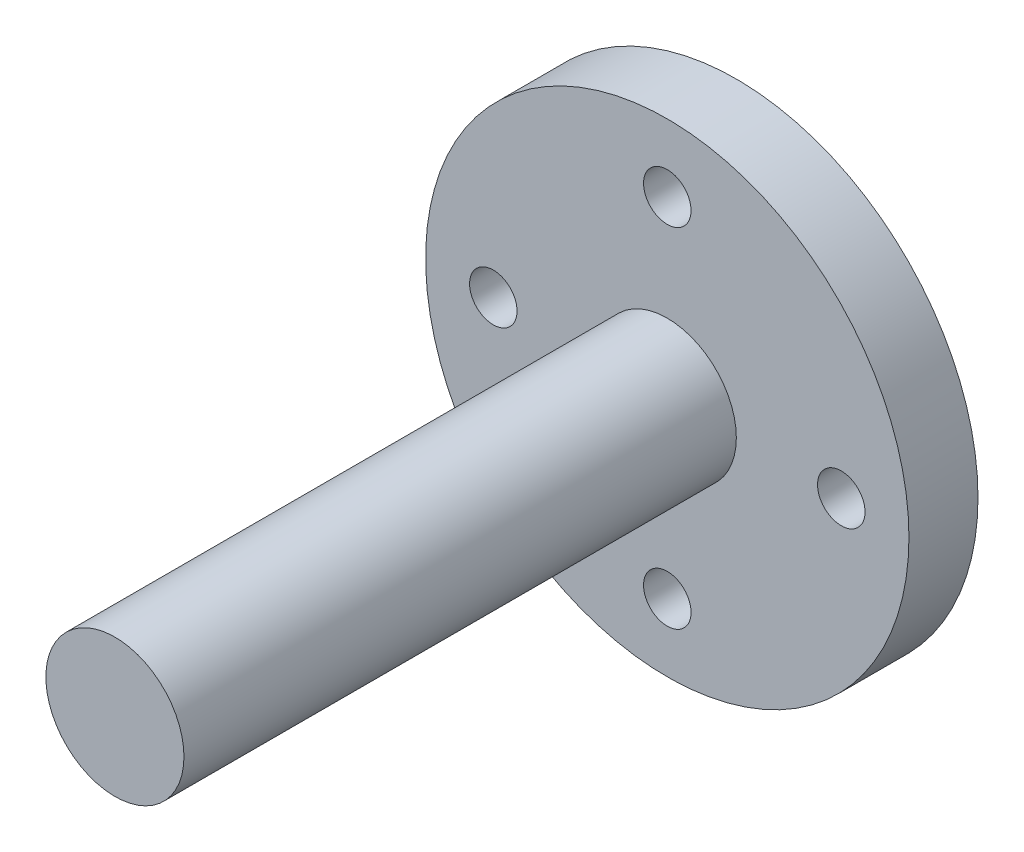
SolidWorks part; units mm, degrees
ref_plane "Front Plane" through (0, 0, 0) normal (0, 0, 1) x (1, 0, 0)
ref_plane "Top Plane" through (0, 0, 0) normal (0, 1, 0) x (1, 0, 0)
ref_plane "Right Plane" through (0, 0, 0) normal (1, 0, 0) x (0, 0, -1)
sketch "Sketch1" plane through (0, 0, 0) normal (0, 0, 1) x (1, 0, 0)
  circle A0 centre (0, 0) radius 11.1125
  dimension "D1" = 22.225
extrude "Boss-Extrude1" add sketch "Sketch1" along normal blind 3.175
sketch "Sketch2" plane through (0, 0, 3.175) normal (0, 0, 1) x (1, 0, 0)
  circle A0 centre (0, 0) radius 3.175
  dimension "D1" = 6.35
extrude "Boss-Extrude2" add sketch "Sketch2" along normal blind 25.4
hole_wizard "#44 (0.086) Diameter Hole1" positions "Sketch4" profile "Sketch3" hole size "#44" standard "ANSI Inch" end condition through all
sketch "Sketch4" plane through (0, 0, 3.175) normal (0, 0, 1) x (1, 0, 0)
  line L0 (0, 8) -> (0, -8) construction
  line L1 (-8, 0) -> (8, 0) construction
  point P0 (0, 8)
  point P4 (0, -8)
  point P14 (-8, 0)
  point P15 (8, 0)
  point P17 (0, 0)
  dimension "D1" = 16
sketch "Sketch3" plane through (0, 8, 3.175) normal (1, 0, 0) x (0, -1, 0)
  line L0 (0, 0) -> (0, 3.175)
  line L1 (0, 3.175) -> (1.0922, 3.175)
  line L2 (1.0922, 3.175) -> (1.0922, 0)
  line L5 (1.0922, 0) -> (0, 0)
  line L11 (0, -6.35) -> (0, 107.95) construction
  dimension "Thru Hole Dia." = 2.1844
  dimension "Thru Hole Depth" = 3.175
